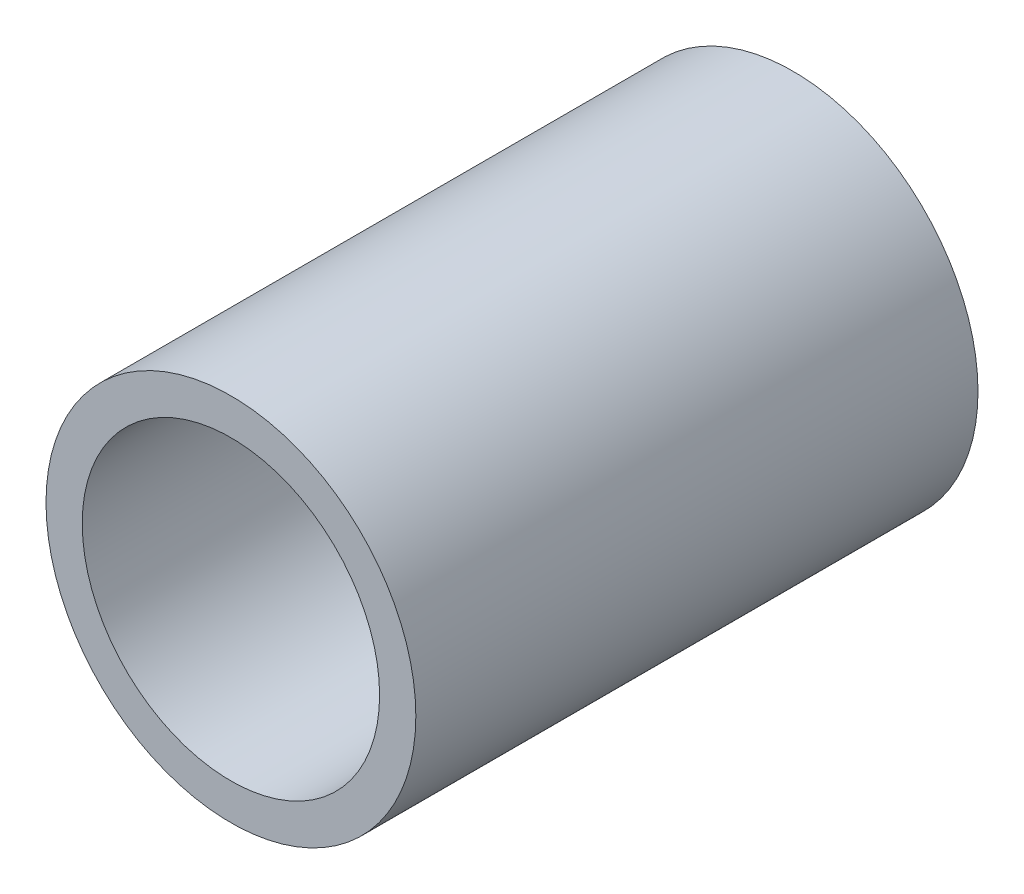
SolidWorks part; units mm, degrees
ref_plane "Front Plane" through (0, 0, 0) normal (0, 0, 1) x (1, 0, 0)
ref_plane "Top Plane" through (0, 0, 0) normal (0, 1, 0) x (1, 0, 0)
ref_plane "Right Plane" through (0, 0, 0) normal (1, 0, 0) x (0, 0, -1)
sketch "Sketch1" plane through (0, 0, 0) normal (0, 0, 1) x (1, 0, 0)
  line L0 (6.35, 0) -> (-6.35, 0) construction
  line L1 (0, -5.1054) -> (0, 5.1054) construction
  line L2 (0, -6.35) -> (0, 6.35) construction
  circle A0 centre (0, 0) radius 6.35 construction
  circle A1 centre (0, 0) radius 5.1054 construction
  point P6 (0, 0)
  point P7 (-5.1054, 0)
  point P8 (5.1054, 0)
  point P10 (-6.35, 0)
  point P11 (6.35, 0)
  point P14 (0, 0)
  point P17 (0, 0)
  point P18 (0, 5.1054)
  point P19 (0, 6.35)
  point P20 (0, -5.1054)
  point P21 (0, -6.35)
  dimension "OD" = 12.7
  dimension "ID" = 10.2108
  dimension "Wall Thickness" = 1.2446
sketch "Sketch2" plane through (0, 0, 0) normal (1, 0, 0) x (0, 0, -1)
  line L0 (0, -5.1054) -> (0, 5.1054) construction
  line L1 (0, -5.1054) -> (0, 5.1054) construction
  line L2 (0, -6.35) -> (0, 6.35) construction
  line L3 (0, -6.35) -> (0, 6.35) construction
  line L4 (9.652, 6.35) -> (-9.652, 6.35) construction
  line L5 (9.652, 5.1054) -> (-9.652, 5.1054) construction
  line L6 (9.652, -5.1054) -> (-9.652, -5.1054) construction
  line L7 (9.652, -6.35) -> (-9.652, -6.35) construction
  line L8 (-9.652, -6.35) -> (-9.652, 6.35) construction
  line L9 (9.652, 6.35) -> (9.652, -6.35) construction
  line L10 (9.652, 0) -> (-9.652, 0) construction
  line L11 (-4.0076, -6.35) -> (-4.0076, 6.35) construction
  line L12 (4.0076, -6.35) -> (4.0076, 6.35) construction
  point P7 (0, 6.35)
  point P10 (0, 5.1054)
  point P13 (0, -5.1054)
  point P16 (0, -6.35)
  point P17 (-9.652, -6.35)
  point P18 (-9.652, -5.1054)
  point P19 (-9.652, 5.1054)
  point P20 (-9.652, 6.35)
  point P21 (9.652, 6.35)
  point P22 (9.652, 5.1054)
  point P23 (9.652, -5.1054)
  point P24 (9.652, -6.35)
  point P28 (0, 0)
  point P30 (-4.0076, 0)
  point P31 (-4.0076, -6.35)
  point P32 (-4.0076, 6.35)
  point P35 (4.0076, 0)
  point P36 (4.0076, 6.35)
  point P37 (4.0076, -6.35)
  dimension "Length" = 19.304
  dimension "Break Line" = 5.6444
sketch "Sketch3" plane through (0, 0, 0) normal (0, 0, 1) x (1, 0, 0)
  circle A0 centre (0, 0) radius 5.1054 construction
  circle A1 centre (0, 0) radius 6.35 construction
  circle A2 centre (0, 0) radius 5.1054
  circle A3 centre (0, 0) radius 6.35
extrude "Boss-Extrude1" add sketch "Sketch3" along normal up to vertex (9.652 mm away) and the other way up to vertex (9.652 mm away) up to point (0, 0, 9.652) other way up to point (0, 0, -9.652)
equation "\"Break Line@Sketch2\"=\"OD@Sketch1\"/2.25"
